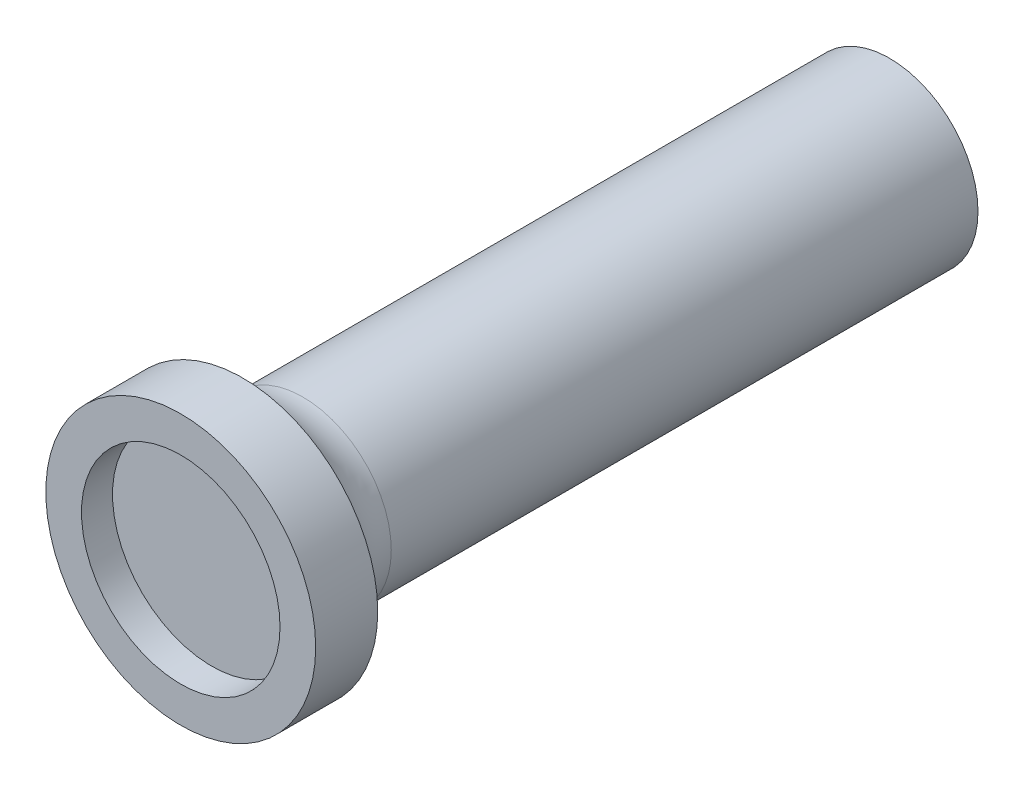
SolidWorks part; units mm, degrees
material "ABS"
ref_plane "Plan de face" through (0, 0, 0) normal (0, 0, 1) x (1, 0, 0)
ref_plane "Plan de dessus" through (0, 0, 0) normal (0, 1, 0) x (1, 0, 0)
ref_plane "Plan de droite" through (0, 0, 0) normal (1, 0, 0) x (0, 0, -1)
sketch "Esquisse1" plane through (0, 0, 0) normal (0, 0, 1) x (1, 0, 0)
  circle A0 centre (0, 0) radius 2.85
  dimension "D1" = 5.7
extrude "Shape" add sketch "Esquisse1" along normal blind 20.85
sketch "Esquisse2" plane through (0, 0, 20.85) normal (0, 0, 1) x (1, 0, 0)
  circle A0 centre (0, 0) radius 4.35
  circle A1 centre (0, 0) radius 2.85 construction
  dimension "D1" = 1.5
extrude "Boss.-Extru.2" add sketch "Esquisse2" along normal blind 2
sketch "Esquisse3" plane through (0, 0, 22.85) normal (0, 0, 1) x (1, 0, 0)
  circle A0 centre (0, 0) radius 3.2
  dimension "D1" = 6.4
extrude "Enlèv. mat.-Extru.1" cut sketch "Esquisse3" against normal blind 1
fillet "Congé1" radius 2 1 edges at (2.85, 0, 20.85)
sketch "Esquisse4" plane through (0, 0, 0) normal (0, 0, -1) x (-1, 0, 0)
  circle A0 centre (0, 0) radius 0.8
  dimension "D1" = 1.6
extrude "AlignBeam" add sketch "Esquisse4" along normal blind 0.8
equation "\"D1@Esquisse1\"=6 - \"errorCircle_tight\""
equation "\"entretoiseBearing\"= 1.5mm"
equation "\"length_tibia\"= 206mm"
equation "\"length_femur\"= 117mm"
equation "\"length_coxa\"= 27mm"
equation "\"height\"= 40mm"
equation "\"width\"= 100mm"
equation "\"lever\"= 40mm"
equation "\"errorFlat\"= 0.20mm"
equation "\"errorFlat_tight\"= 0.15mm"
equation "\"errorCircle\"= 0.40mm"
equation "\"errorCircle_tight\" = 0.30mm"
equation "\"cuticule\"=1.5mm"
equation "\"cuticule_attach_w\"=10mm"
equation "\"cuticule_attach_h\"=2.5mm"
equation "\"depthMagnet\"= 1mm"
equation "\"insert_d\" = 3.2mm"
equation "\"insert_l\" = 5mm"
equation "\"D1@Esquisse3\"= 6 + \"errorCircle\""
equation "\"D1@Esquisse4\"= 2 - \"errorCircle\""
equation "\"D1@AlignBeam\" = 1 - \"errorFlat\""
